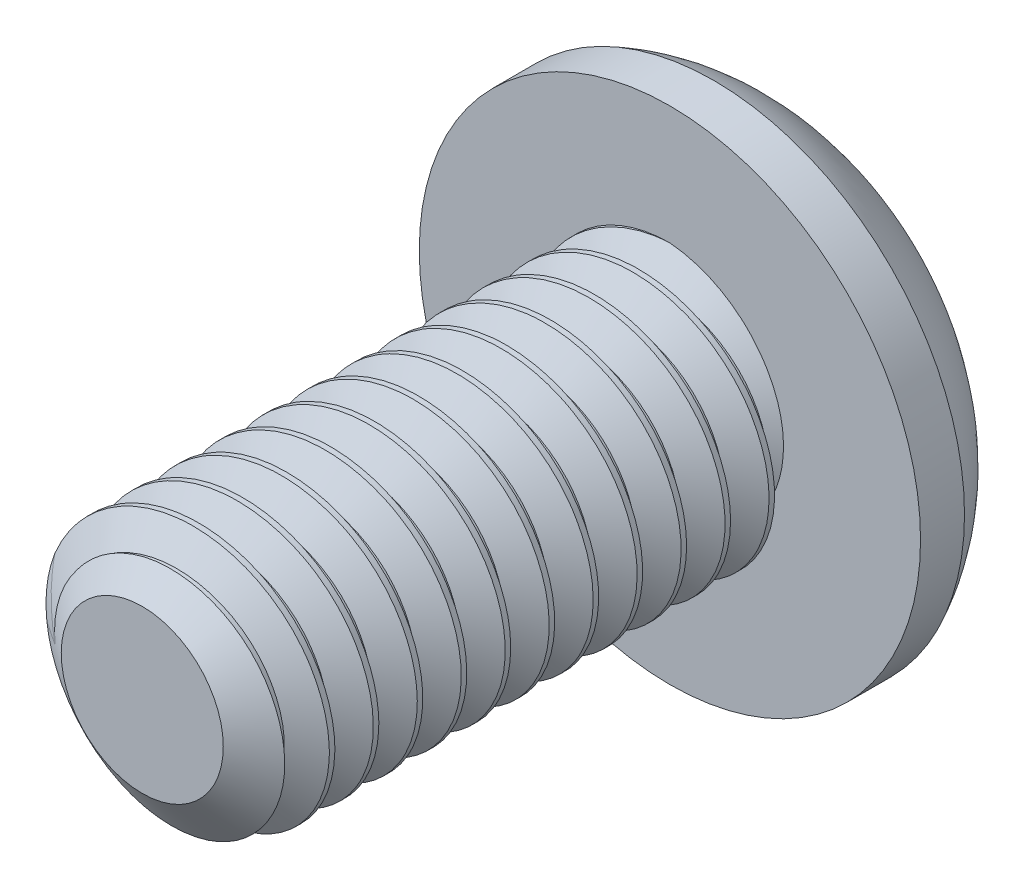
SolidWorks part; units mm, degrees
ref_plane "Front Plane" through (0, 0, 0) normal (0, 0, 1) x (1, 0, 0)
ref_plane "Top Plane" through (0, 0, 0) normal (0, 1, 0) x (1, 0, 0)
ref_plane "Right Plane" through (0, 0, 0) normal (1, 0, 0) x (0, 0, -1)
sketch "Sketch1" plane through (0, 0, 0) normal (0, 0, 1) x (1, 0, 0)
  circle A0 centre (0, 0) radius 1.5
  dimension "OD" = 3
extrude "Extrude1" add sketch "Sketch1" against normal blind 6
sketch "Sketch2" plane through (0, 0, 0) normal (0, 0, 1) x (1, 0, 0)
  circle A0 centre (0, 0) radius 1.5 construction
  circle A1 centre (0, 0) radius 1.5
curve "Helix/Spiral1" pitch 0.5 height 6.5 radius 1.5 centre (0, 0, 0) axis (0, 0, -1) start towards (0, 1, 0) parameters "pitch"=0.5
sketch "Sketch3" plane through (0, 0, 0) normal (1, 0, 0) x (0, 0, -1)
  line L0 (-0.4375, 1.5) -> (-0.25, 1.1752)
  line L1 (-0.25, 1.1752) -> (-0.1875, 1.1752)
  line L2 (-0.1875, 1.1752) -> (0, 1.5)
  line L3 (-0.4375, 1.5) -> (0, 1.5)
  line L4 (-0.2187, 1.5) -> (-0.2187, 1.1752) construction
  line L5 (-0.3437, 1.3376) -> (-0.0937, 1.3376) construction
  line L6 (0, 1.5) -> (0, -1.5) construction
  dimension "D1" = 0.0625
  dimension "D2" = 0.25
  dimension "D3" = 60
sweep "Cut-Sweep1" cut profiles "Sketch3" path "Helix/Spiral1"
sketch "Sketch4" plane through (0, 0, 0) normal (1, 0, 0) x (0, 0, -1)
  line L0 (0.4053, 1.5) -> (0, 0.9212)
  line L1 (0, 0.9212) -> (0, 1.5)
  line L2 (0.4053, 1.5) -> (0, 1.5)
  line L3 (-0.4375, 1.5) -> (0, 1.5) construction
  line L4 (0, 0) -> (7.0209, 0) construction
  dimension "D1" = 55
  dimension "D2" = 0.254
revolve "Cut-Revolve1" cut sketch "Sketch4" angle 360 about L4
sketch "Sketch5" plane through (0, 0, 0) normal (1, 0, 0) x (0, 0, -1)
  line L0 (6, -1.1822) -> (6, 1.0703) construction
  line L1 (6, 1.627) -> (28.1202, 1.627)
  line L2 (6, 1.627) -> (6, 0)
  line L3 (6, 0) -> (28, 0)
  line L4 (28, 1.2968) -> (28, 0)
  line L5 (28.1202, 1.627) -> (28, 1.2968)
  line L6 (0, 0) -> (9.9695, 0) construction
  point P3 (28, 1.627)
  point P10 (28, 1.627)
  dimension "D1" = 0.3302
  dimension "Thread min" = 28
  dimension "D2" = 0.127
  dimension "D3" = 20
revolve "partially thread" add sketch "Sketch5" angle 360 about L6
sketch "Sketch6" plane through (0, 0, -6) normal (0, 0, -1) x (-1, 0, 0)
  circle A0 centre (0, 0) radius 2.85
  dimension "head dia" = 5.7
extrude "Extrude2" add sketch "Sketch6" along normal blind 1.65
sketch "Sketch10" plane through (0, 0, 0) normal (1, 0, 0) x (0, 0, -1)
  line L0 (7.65, -2.85) -> (7.65, 2.85) construction
  line L1 (0, 0) -> (15.9584, 0) construction
  line L2 (7.65, 2.85) -> (6, 2.85) construction
  line L3 (6, 2.85) -> (6, -2.85) construction
  line L4 (6.5, 2.85) -> (6.5, 3.35)
  line L5 (6.5, 3.35) -> (8.15, 3.35)
  line L6 (8.15, 3.35) -> (8.15, 1)
  line L7 (7.65, 1) -> (8.15, 1)
  arc A0 (7.65, 1) -> (6.5, 2.85) centre (5.587, 1) ccw
  dimension "D1" = 2
  dimension "D2" = 0.5
  dimension "D3" = 0.5
revolve "Cut-Revolve2" cut sketch "Sketch10" angle 360 about L1
ref_plane "Plane1" through (0, 0, -7.65) normal (0, 0, 1) x (1, 0, 0)
sketch "Sketch7" plane through (0, 0, -7.65) normal (0, 0, -1) x (-1, 0, 0)
  line L1 (0, 1.1547) -> (-1, 0.5774)
  line L2 (-1, 0.5774) -> (-1, -0.5774)
  line L3 (-1, -0.5774) -> (0, -1.1547)
  line L4 (0, -1.1547) -> (1, -0.5774)
  line L5 (1, -0.5774) -> (1, 0.5774)
  line L6 (1, 0.5774) -> (0, 1.1547)
  circle A0 centre (0, 0) radius 1 construction
  dimension "hex dia" = 2
extrude "Cut-Extrude1" cut sketch "Sketch7" against normal blind 1.5
sketch "Sketch8" plane through (0, 0, -7.65) normal (0, 0, 1) x (1, 0, 0)
  circle A0 centre (0, 0) radius 1.1547
extrude "Cut-Extrude2" cut sketch "Sketch8" along normal through all draft 45
sketch "Sketch9" plane through (0, 0, 0) normal (1, 0, 0) x (0, 0, -1)
  line L0 (0, 1.5) -> (0, -1.5) construction
  line L1 (2.75, 1.5) -> (2.75, -1.5) construction
  dimension "D1" = 2.75
  dimension "D4" = 0.635
  dimension "D5" = 0.3302
equation "\"D3@Helix/Spiral1\" = \"screw length@Extrude1\"+\"pitch@Helix/Spiral1\""
equation "\"D1@Sketch3\" = \"pitch@Helix/Spiral1\"*.125"
equation "\"D2@Sketch3\" = \"pitch@Helix/Spiral1\"*.5"
equation "\"D1@Cut-Extrude1\" = \"hex dia@Sketch7\"*.75"
equation "\"D1@Sketch9\" = \"pitch@Helix/Spiral1\"*5.5"
equation "\"D1@Sketch10\" = \"hex dia@Sketch7\""
equation "\"D1@Plane1\" = \"head depth@Extrude2\""
